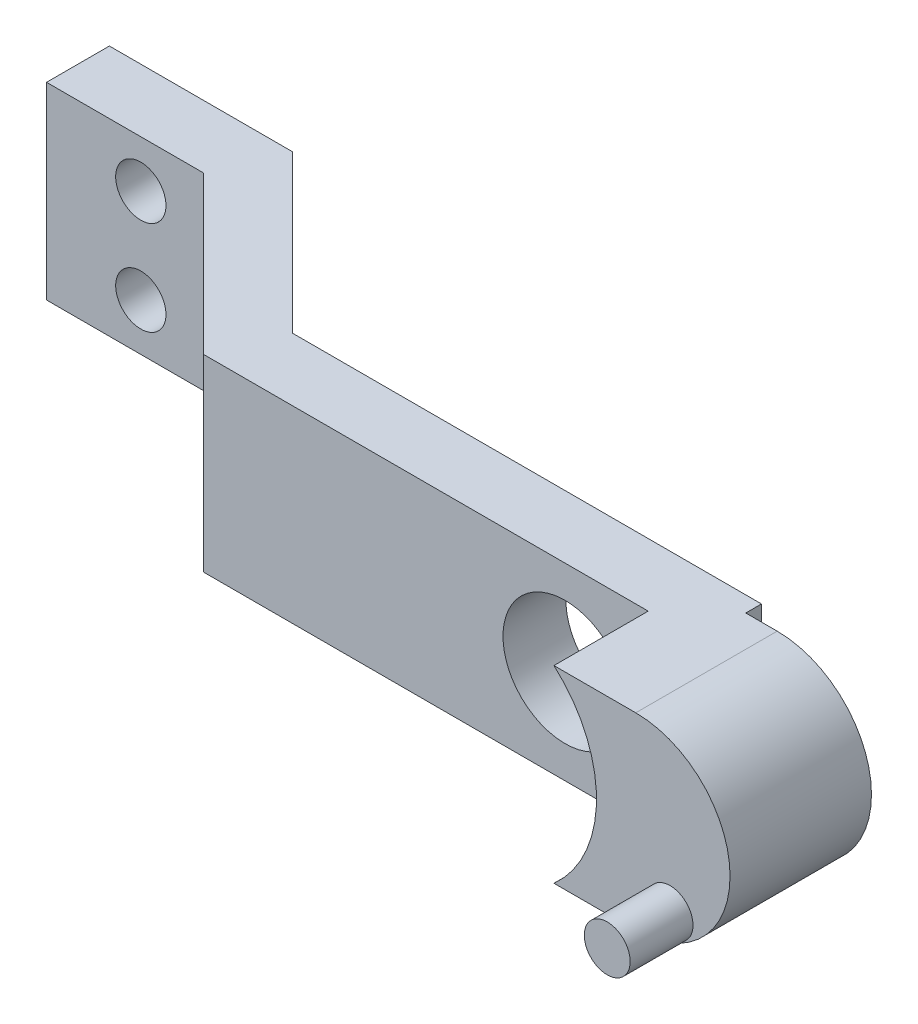
SolidWorks part; units mm, degrees
ref_plane "Front Plane" through (0, 0, 0) normal (0, 0, 1) x (1, 0, 0)
ref_plane "Top Plane" through (0, 0, 0) normal (0, 1, 0) x (1, 0, 0)
ref_plane "Right Plane" through (0, 0, 0) normal (1, 0, 0) x (0, 0, -1)
sketch "Sketch1" plane through (0, 0, 0) normal (0, 0, 1) x (1, 0, 0)
  line L0 (0, 0) -> (16.5, 0) construction
  line L1 (-23, 6) -> (16.5, 6)
  line L2 (-23, 6) -> (-23, -6)
  line L3 (-23, -6) -> (16.5, -6)
  line L4 (16.5, 6) -> (16.5, -6)
  line L5 (0, 0) -> (-23, 0) construction
  line L6 (0, 0) -> (0, -6) construction
  line L7 (0, 0) -> (0, 6) construction
  circle A0 centre (0, 0) radius 3.95
  dimension "D1" = 7.9
  dimension "D2" = 6
  dimension "D3" = 23
  dimension "D4" = 16.5
extrude "Boss-Extrude1" add sketch "Sketch1" along normal blind 4
sketch "Sketch3" plane through (0, -6, 0) normal (0, -1, 0) x (1, 0, 0)
  line L0 (-23, 4) -> (-33, -6)
  line L2 (-31.3431, -10) -> (-21.3431, 0)
  line L3 (-23, 0) -> (16.5, 0) construction
  line L4 (-23, 4) -> (-21.3431, 0)
  line L5 (-23, 4) -> (-23, 0) construction
  line L6 (-33, -6) -> (-43, -6)
  line L7 (-43, -6) -> (-43, -10)
  line L8 (-43, -10) -> (-31.3431, -10)
  dimension "D1" = 4
  dimension "D2" = 4
  dimension "D3" = 45
  dimension "D4" = 20
  dimension "D5" = 10
extrude "Boss-Extrude3" add sketch "Sketch3" against normal up to surface (12 mm away) up to face at (-3.25, 6, 2)
sketch "Sketch4" plane through (0, 0, -6) normal (0, 0, 1) x (1, 0, 0)
  line L1 (-37, -3) -> (-37, 3) construction
  line L2 (-37, 3) -> (-37, 6) construction
  line L3 (-43, 6) -> (-33, 6) construction
  line L4 (-37, -3) -> (-37, -6) construction
  line L5 (-33, -6) -> (-43, -6) construction
  circle A0 centre (-37, 3) radius 1.6
  circle A1 centre (-37, -3) radius 1.6
  dimension "D1" = 3.2
  dimension "D3" = 6
  dimension "D2" = 37
extrude "Cut-Extrude1" cut sketch "Sketch4" against normal through all
fillet "Fillet1" radius 6 2 edges at (16.5, 6, 2) (16.5, -6, 2)
sketch "Sketch7" plane through (0, 0, 4) normal (0, 0, 1) x (1, 0, 0)
  line L0 (10.5, 6) -> (-23, 6) construction
  line L1 (-23, -6) -> (10.5, -6) construction
  line L2 (5.2915, -6) -> (10.5, -6)
  line L3 (10.5, 6) -> (5.2915, 6)
  arc A0 (10.5, 6) -> (10.5, -6) centre (10.5, 0) cw
  arc A1 (10.5, -6) -> (16.5, 0) centre (10.5, 0) ccw construction
  arc A2 (5.2915, 6) -> (5.2915, -6) centre (0, 0) cw
  dimension "D1" = 8
extrude "Boss-Extrude5" add sketch "Sketch7" along normal blind 6
sketch "Sketch5" plane through (0, 0, 10) normal (0, 0, 1) x (1, 0, 0)
  circle A0 centre (12.6832, -3.8928) radius 1.46
  dimension "D1" = 2.92
  dimension "D2" = 12.6832
  dimension "D3" = 3.8928
extrude "Boss-Extrude4" add sketch "Sketch5" along normal blind 4
sketch "Sketch6" plane through (0, -6, 0) normal (0, -1, 0) x (1, 0, 0)
  line L0 (10.5, 0) -> (16.5, 0) construction
  line L1 (8.5, 1) -> (16.5, 1)
  line L2 (8.5, 1) -> (8.5, 0)
  line L3 (8.5, 0) -> (16.5, 0)
  line L4 (16.5, 1) -> (16.5, 0)
  line L5 (16.5, 4) -> (16.5, 0) construction
  dimension "D1" = 1
  dimension "D2" = 8
extrude "Cut-Extrude3" cut sketch "Sketch6" against normal through all
